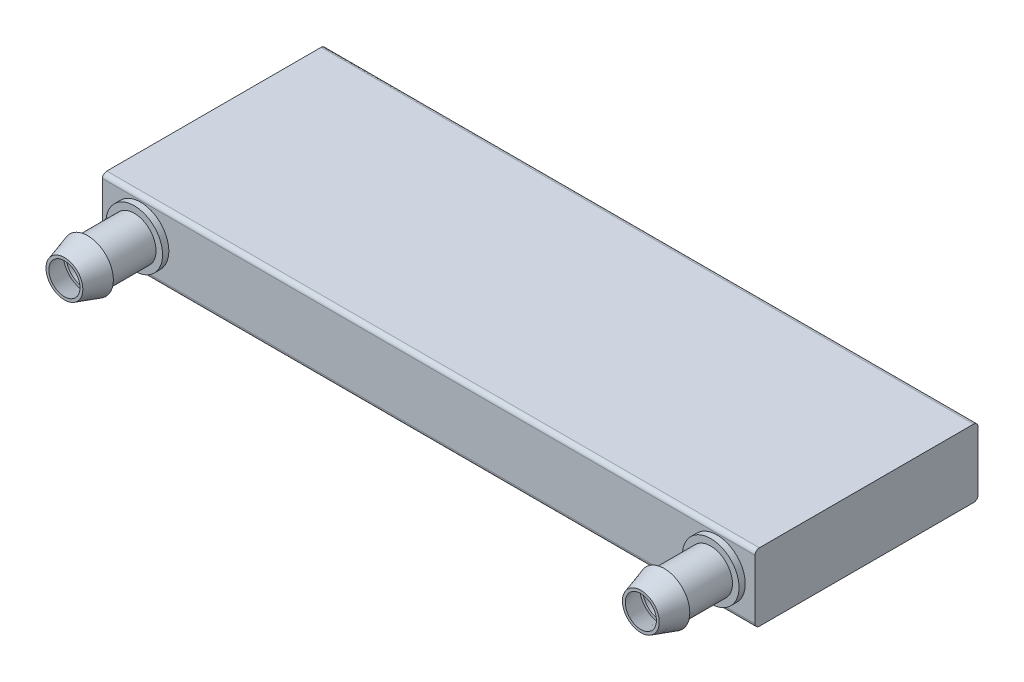
SolidWorks part; units mm, degrees
ref_plane "Front Plane" through (0, 0, 0) normal (0, 0, 1) x (1, 0, 0)
ref_plane "Top Plane" through (0, 0, 0) normal (0, 1, 0) x (1, 0, 0)
ref_plane "Right Plane" through (0, 0, 0) normal (1, 0, 0) x (0, 0, -1)
sketch "Sketch1" plane through (0, 0, 0) normal (0, 1, 0) x (1, 0, 0)
  line L1 (60, -20.5) -> (-60, -20.5)
  line L2 (60, -20.5) -> (60, 20.5)
  line L3 (60, 20.5) -> (-60, 20.5)
  line L4 (-60, -20.5) -> (-60, 20.5)
  line L5 (60, -20.5) -> (-60, 20.5) construction
  line L6 (60, 20.5) -> (-60, -20.5) construction
  point P0 (0, 0)
  dimension "D1" = 41
  dimension "D2" = 120
extrude "Boss-Extrude1" add sketch "Sketch1" along normal blind 12.5
sketch "Sketch2" plane through (0, 0, 20.5) normal (0, 0, 1) x (1, 0, 0)
  line L0 (53, 12.5) -> (53, 0) construction
  line L1 (-60, 12.5) -> (60, 12.5) construction
  line L2 (-60, 0) -> (60, 0) construction
  line L3 (60, 12.5) -> (60, 0) construction
  circle A0 centre (53, 6.25) radius 5.2
  dimension "D1" = 10.4
  dimension "D2" = 7
extrude "Boss-Extrude2" add sketch "Sketch2" along normal blind 1.15
sketch "Sketch3" plane through (0, 0, 21.65) normal (0, 0, 1) x (1, 0, 0)
  circle A0 centre (53, 6.25) radius 4
  dimension "D1" = 8
extrude "Boss-Extrude3" add sketch "Sketch3" along normal blind 8.55
sketch "Sketch4" plane through (0, 0, 30.2) normal (0, 0, 1) x (1, 0, 0)
  circle A0 centre (53, 6.25) radius 4.7
  dimension "D1" = 9.4
extrude "Boss-Extrude4" add sketch "Sketch4" along normal blind 4.3 draft 17
mirror "Mirror1" about plane through (0, 0, 0) normal (1, 0, 0) of "Boss-Extrude4", "Boss-Extrude3", "Boss-Extrude2"
fillet "Fillet1" radius 0.8 4 edges at (0, 12.5, -20.5) (0, 12.5, 20.5) (0, 0, 20.5) (0, 0, -20.5)
shell "Shell1" thickness 0.5 removed face at (56.3854, 6.25, 34.5) removed face at (-49.6146, 6.25, 34.5)
sketch "Sketch5" plane through (0, 0, 0) normal (0, -1, 0) x (1, 0, 0)
  line L0 (0, 0) -> (-60, 0) construction
  line L2 (-60, -19.7) -> (-60, 19.7) construction
  line L3 (0, -19.7) -> (0, 19.7) construction
  line L4 (60, -19.7) -> (-60, -19.7) construction
  line L5 (-60, 19.7) -> (60, 19.7) construction
  line L6 (0, 0) -> (60, 0) construction
  line L7 (60, 19.7) -> (60, -19.7) construction
  point P2 (-30, 0)
  point P3 (30, 0)
sketch "Sketch6" plane through (0, 12.5, 0) normal (0, 1, 0) x (1, 0, 0)
  point P0 (30, 0)
  point P2 (-30, 0)
ref_point "Point1"
ref_point "Point2"
ref_point "Point3"
ref_point "Point4"
ref_axis "Axis1" through (-30, 12.5, 0) along (0, -1, 0)
ref_axis "Axis2" through (30, 12.5, 0) along (0, -1, 0)
